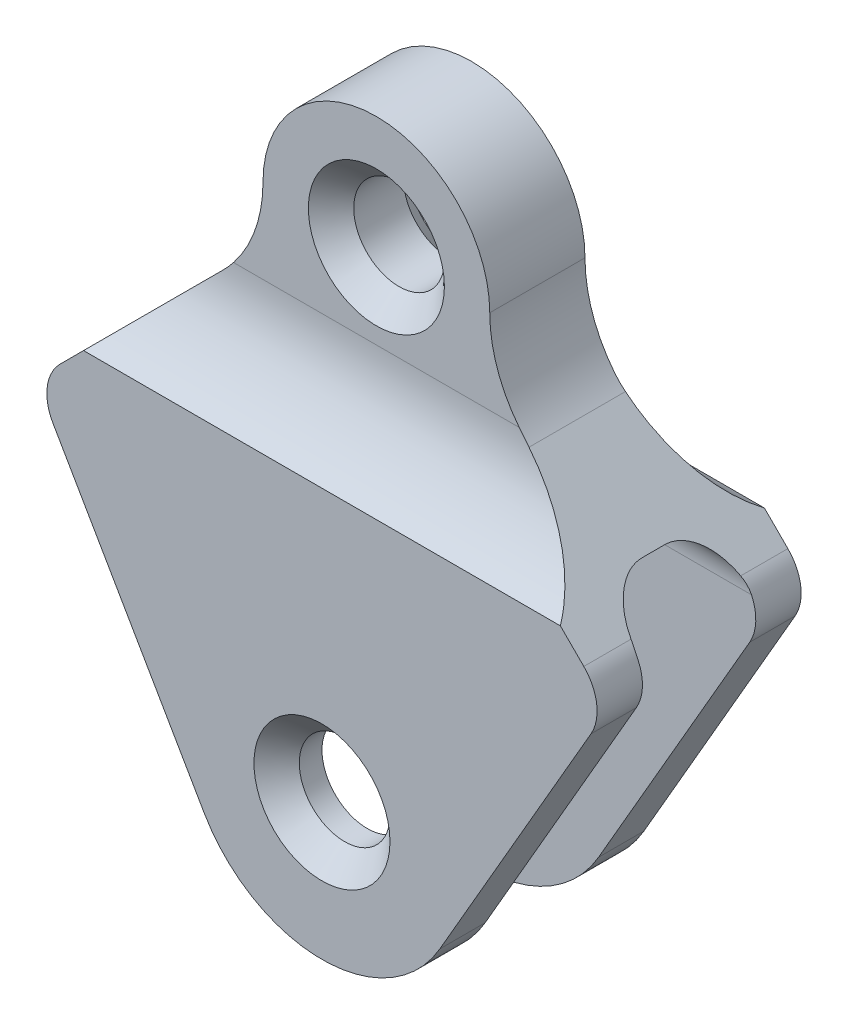
SolidWorks part; units mm, degrees
ref_plane "Front Plane" through (0, 0, 0) normal (0, 0, 1) x (1, 0, 0)
ref_plane "Top Plane" through (0, 0, 0) normal (0, 1, 0) x (1, 0, 0)
ref_plane "Right Plane" through (0, 0, 0) normal (1, 0, 0) x (0, 0, -1)
sketch "Sketch1" plane through (0, 0, 0) normal (0, 0, 1) x (1, 0, 0)
  line L0 (0, 0) -> (0, 100) construction
  line L1 (25.9808, -15) -> (59.3297, 42.762)
  line L2 (33.7868, 78.7868) -> (57.7405, 54.8331)
  line L3 (0, 100) -> (73.4292, 100) construction
  line L4 (-33.7868, 78.7868) -> (-57.7405, 54.8331)
  line L5 (-25.9808, -15) -> (-59.3297, 42.762)
  line L6 (-52.5736, 60) -> (52.5736, 60)
  circle A1 centre (0, 0) radius 10
  arc A2 (-25.9808, -15) -> (25.9808, -15) centre (0, 0) ccw
  arc A3 (25, 100) -> (-25, 100) centre (0, 100) ccw
  circle A4 centre (0, 100) radius 10
  arc A5 (57.7405, 54.8331) -> (59.3297, 42.762) centre (50.6694, 47.762) cw
  arc A6 (33.7868, 78.7868) -> (25, 100) centre (55, 100) cw
  arc A7 (-33.7868, 78.7868) -> (-25, 100) centre (-55, 100) ccw
  arc A8 (-57.7405, 54.8331) -> (-59.3297, 42.762) centre (-50.6694, 47.762) ccw
  point P14 (0, -30)
  point P23 (52.5736, 60)
  point P24 (-52.5736, 60)
  dimension "D1" = 20
  dimension "D2" = 60
  dimension "D4" = 50
  dimension "D5" = 20
  dimension "D6" = 30
  dimension "D8" = 10
  dimension "D3" = 100
  dimension "D7" = 45
  dimension "D9" = 30
  dimension "D10" = 90
extrude "Boss-Extrude1" add sketch "Sketch1" along normal blind 10.5 and the other way blind 10.5 contours A7 L4 L6 L2 A6 A3 A4 region at (0, 84.5787, 0)
extrude "Boss-Extrude2" add sketch "Sketch1<3>" along normal blind 22.5 and the other way blind 22.5 contours L4 A8 L5 A2 L1 A5 L2 L6 A1 region at (0, 24.8555, 0)
sketch "Sketch1<3>" plane through (0, 0, 0) normal (0, 0, 1) x (1, 0, 0) same geometry as "Sketch1"
chamfer "Chamfer1" distance 5 angle 45 4 edges at (10, 0, -22.5) (10, 0, 22.5) (10, 100, -10.5) (10, 100, 10.5)
fillet "Fillet1" radius 25 2 edges at (0, 60, 10.5) (0, 60, -10.5)
sketch "Sketch2" plane through (0, 0, 0) normal (1, 0, 0) x (0, 0, -1)
  line L0 (-12.5, -30) -> (12.5, -30)
  line L1 (-22.5, -30) -> (22.5, -30) construction
  line L2 (12.5, -30) -> (12.5, 52)
  line L3 (-12.5, -30) -> (-12.5, 52)
  line L4 (0, 38.6072) -> (0, -37.1746) construction
  line L5 (-2.5, 62) -> (2.5, 62)
  arc A0 (-12.5, 52) -> (-2.5, 62) centre (-2.5, 52) cw
  arc A2 (2.5, 62) -> (12.5, 52) centre (2.5, 52) cw
  dimension "D2" = 10
  dimension "D3" = 92
  dimension "D1" = 25
extrude "Cut-Extrude1" cut sketch "Sketch2" against normal blind 80 and the other way blind 80
